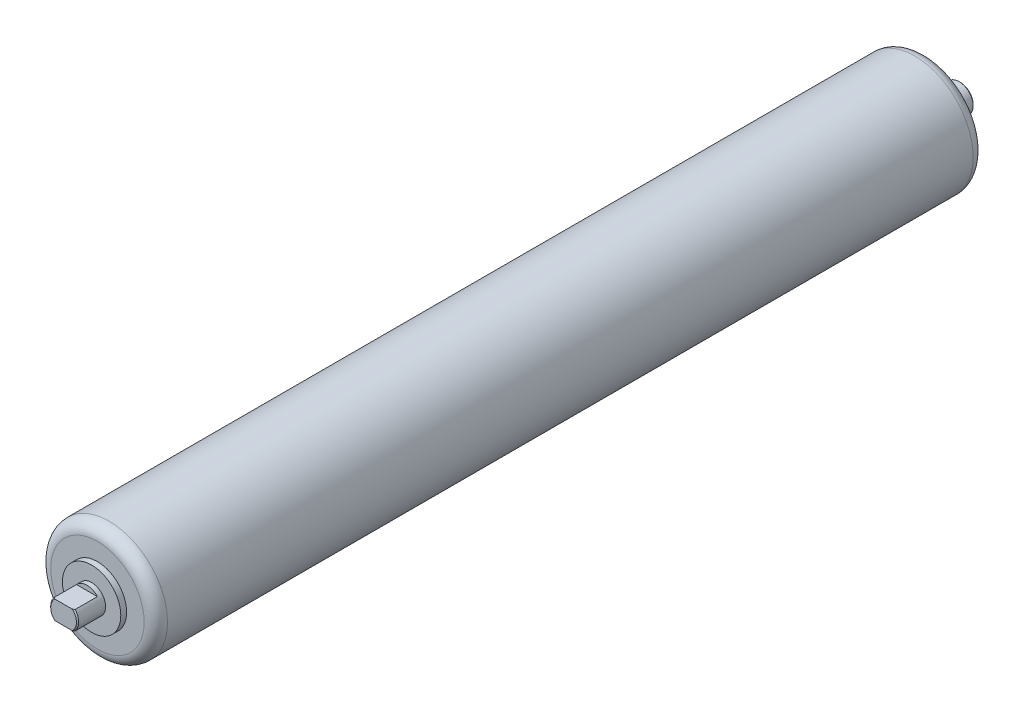
SolidWorks part; units mm, degrees
ref_plane "Front Plane" through (0, 0, 0) normal (0, 0, 1) x (1, 0, 0)
ref_plane "Top Plane" through (0, 0, 0) normal (0, 1, 0) x (1, 0, 0)
ref_plane "Right Plane" through (0, 0, 0) normal (1, 0, 0) x (0, 0, -1)
sketch "Sketch1" plane through (0, 0, 0) normal (0, 1, 0) x (1, 0, 0)
  line L0 (5.5, 14.5) -> (0, 14.5)
  line L1 (0, 14.5) -> (0, -369.5)
  line L2 (0, -369.5) -> (5.5, -369.5)
  line L3 (5.5, -369.5) -> (6, -369)
  line L4 (6, -369) -> (6, -357.5)
  line L5 (6, -357.5) -> (12.5, -357.5)
  line L6 (12.5, -357.5) -> (12.5, -355)
  line L7 (12.5, -355) -> (25, -355)
  line L8 (25, -355) -> (25, 0)
  line L9 (25, 0) -> (12.5, 0)
  line L10 (12.5, 0) -> (12.5, 2.5)
  line L11 (12.5, 2.5) -> (6, 2.5)
  line L12 (6, 2.5) -> (6, 14)
  line L13 (6, 14) -> (5.5, 14.5)
  line L14 (0, 14.5) -> (0, -369.5) construction
revolve "Revolve1" add sketch "Sketch1" angle 360 about L14 reverse direction yes
fillet "Fillet1" radius 5 2 edges at (25, 0, 355) (25, 0, 0)
sketch "Sketch2" plane through (0, 0, 369.5) normal (0, 0, 1) x (1, 0, 0)
  line L0 (-4.4721, 4) -> (5.9555, 4)
  line L1 (-4.4721, -4) -> (4.4721, -4)
  circle A0 centre (0, 0) radius 6 construction
  arc A1 (4.4721, 4) -> (-4.4721, 4) centre (0, 0) ccw
  arc A2 (-4.4721, -4) -> (4.4721, -4) centre (0, 0) ccw
  circle M3 centre (0, 0) radius 5.5
  dimension "D1" = 8
  dimension "D2" = 4
extrude "Cut-Extrude1" cut sketch "Sketch2" against normal blind 10 contours L0 A1 M3 | L0 M3 | L1 M3 | L1 A2 M3 region at (0, 5.9083, 369.5) region at (0, 4.6076, 369.5) region at (0, -5.5917, 369.5) region at (0, -4.6076, 369.5)
